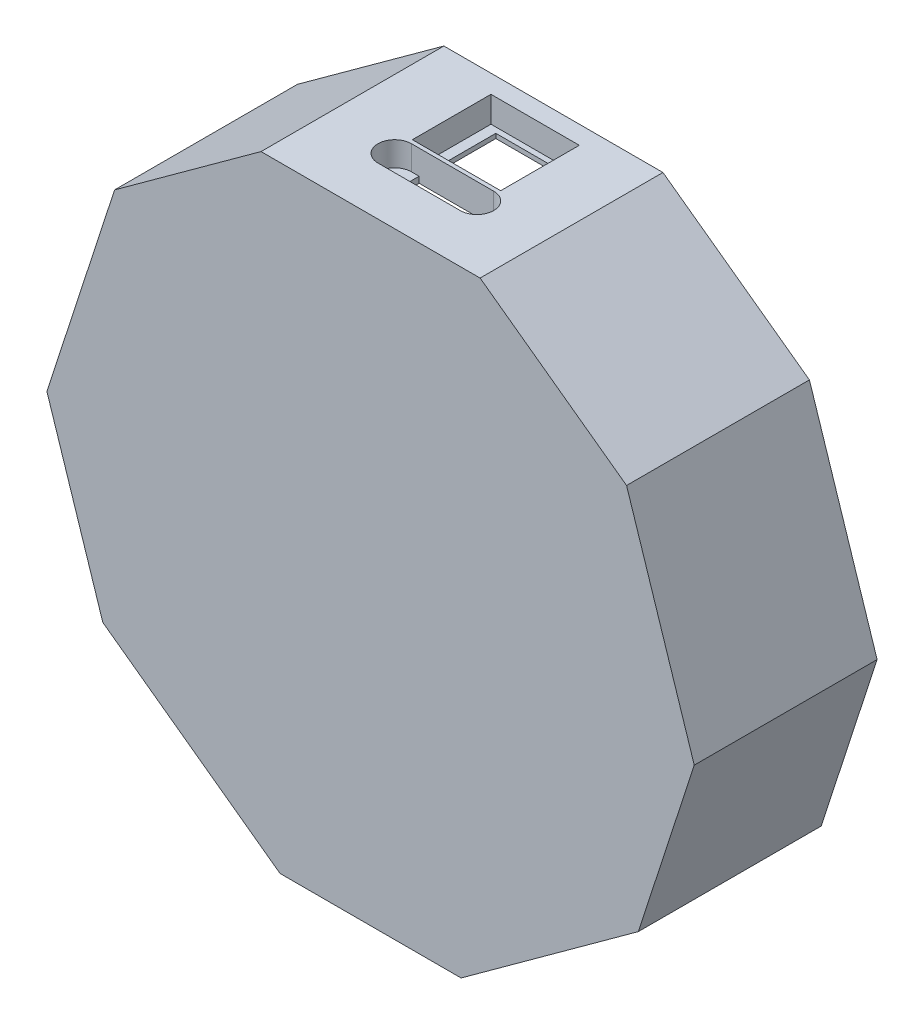
SolidWorks part; units mm, degrees
note: '?' marks a value the reader was unsure of.
ref_plane "Front Plane" through (0, 0, 0) normal (0, 0, 1) x (1, 0, 0)
ref_plane "Top Plane" through (0, 0, 0) normal (0, 1, 0) x (1, 0, 0)
ref_plane "Right Plane" through (0, 0, 0) normal (1, 0, 0) x (0, 0, -1)
sketch "Sketch2" plane through (0, 0, 0) normal (0, 1, 0) x (1, 0, 0)
  line L0 (15.061, 0) -> (15.061, 32)
  line L1 (-12.561, 2.5) -> (12.561, 2.5)
  line L2 (-12.561, 2.5) -> (-12.561, 32)
  line L4 (12.561, 2.5) -> (12.561, 32)
  line L5 (15.061, 32) -> (12.561, 32)
  line L7 (-15.061, 32) -> (-15.061, 0)
  line L8 (-15.061, 0) -> (15.061, 0)
  line L10 (-15.061, 32) -> (-12.561, 32)
  point P4 (0, 2.5)
  point P12 (0, 0)
  dimension "D1" = 2.5
  dimension "D2" = 2.5
  dimension "D3" = 29.5
  dimension "D4" = 25.122
extrude "Boss-Extrude1" add sketch "Sketch2" along normal blind 32.5
sketch "Sketch4" plane through (0, 0, 0) normal (0, -1, 0) x (1, 0, 0)
  line L10 (-7.561, -6) -> (-7.561, 0)
  line L13 (-12.561, -2.5) -> (-12.561, -32) construction
  line L18 (-12.561, -10) -> (-7.561, -6)
  line L23 (12.561, -32) -> (12.561, -2.5) construction
  line L26 (12.561, -10) -> (7.561, -6)
  line L33 (-15.061, -32) -> (-15.061, 0) construction
  line L36 (15.061, 0) -> (15.061, -32) construction
  line L38 (-7.561, 0) -> (-15.061, 0)
  line L39 (7.561, -6) -> (7.561, 0)
  line L40 (7.561, 0) -> (15.061, 0)
  line L41 (-15.061, 0) -> (-15.061, -32)
  line L42 (-15.061, -32) -> (-12.561, -32)
  line L43 (-12.561, -32) -> (-15.061, -32) construction
  line L44 (-12.561, -32) -> (-12.561, -10)
  line L45 (12.561, -10) -> (12.561, -32)
  line L46 (12.561, -32) -> (15.061, -32)
  line L47 (15.061, -32) -> (15.061, 0)
  circle A2 centre (-10.2499, -4.95) radius 1.05
  circle A5 centre (10.2499, -4.95) radius 1.05
  dimension "D4" = 6
  dimension "D5" = 2.1
  dimension "D1" = 7.5
  dimension "D2" = 7.5
  dimension "D3" = 10
extrude "Boss-Extrude2" add sketch "Sketch4" along normal blind 2.5
sketch "Sketch5" plane through (0, 32.5, 0) normal (0, 1, 0) x (1, 0, 0)
  line L0 (-15.061, 32) -> (-10.2499, 32)
  line L9 (-10.2499, 32) -> (-6.25, 26)
  line L13 (-15.061, 0) -> (15.061, 0) construction
  line L14 (15.061, 0) -> (-15.061, 0)
  line L15 (-15.061, 0) -> (-15.061, 32)
  line L20 (15.061, 0) -> (15.061, 32)
  line L21 (-6.25, 26) -> (6.25, 26)
  line L22 (6.25, 26) -> (10.2499, 32)
  line L23 (10.2499, 32) -> (15.061, 32)
  circle A0 centre (-10.2499, 4.95) radius 1.05 construction
  circle A1 centre (-10.2499, 8.7) radius 1.05
  circle A2 centre (10.2499, 8.7) radius 1.05
  point P6 (0, 26)
  dimension "D4" = 0
  dimension "D1" = 8.7
  dimension "D2" = 12.5
  dimension "D3" = 20.4998
  dimension "D5" = 6
extrude "Boss-Extrude3" add sketch "Sketch5" along normal blind 3
sketch "Sketch6" plane through (-15.061, 0, 0) normal (-1, 0, 0) x (0, 0, 1)
  line L0 (-12.5, 35.5) -> (-32, 2.5)
  line L1 (-32, 2.5) -> (-32, 35.5)
  line L2 (-32, 35.5) -> (-12.5, 35.5)
  line L3 (-32, 35.5) -> (-32, -2.5) construction
  line L4 (-32, 35.5) -> (0, 35.5) construction
  line L6 (0, -2.5) -> (-32, -2.5) construction
  line L7 (0, 35.5) -> (0, -2.5) construction
  dimension "D1" = 5
  dimension "D2" = 12.5
extrude "Cut-Extrude1" cut sketch "Sketch6" against normal through all
ref_plane "Plane1" through (0, 16.5, 0) normal (0, -1, 0) x (-1, 0, 0)
sketch "Sketch13" plane through (0, 0, 0) normal (0, 0, 1) x (1, 0, 0)
  line L1 (-15.061, 35.5) -> (15.061, 35.5)
  line L2 (-15.061, 35.5) -> (-15.061, -2.5)
  line L3 (-15.061, -2.5) -> (15.061, -2.5)
  line L4 (15.061, 35.5) -> (15.061, -2.5)
extrude "Boss-Extrude7" add sketch "Sketch13" along normal blind 2.5
sketch "Sketch8" plane through (0, 0, 2.5) normal (0, 0, 1) x (1, 0, 0)
  line L0 (0, -43.5) -> (-43.5926, 16.5)
  line L1 (-16.5671, 16.5) -> (16.5671, 16.5) construction
  line L2 (-43.5926, 16.5) -> (43.5926, 16.5)
  line L3 (43.5926, 16.5) -> (0, -43.5)
  dimension "D1" = 72
  dimension "D2" = 60
extrude "Boss-Extrude4" add sketch "Sketch8" along normal blind 5
sketch "Sketch9" plane through (0, 0, 2.5) normal (0, 0, 1) x (1, 0, 0)
  line L0 (43.5926, 16.5) -> (65.3888, 46.5)
  line L1 (65.3888, 46.5) -> (-65.3888, 46.5)
  line L2 (-65.3888, 46.5) -> (-43.5926, 16.5)
  line L3 (43.5926, 16.5) -> (-43.5926, 16.5)
  line L4 (0, -43.5) -> (43.5926, 16.5) construction
  line L5 (-43.5926, 16.5) -> (0, -43.5) construction
  dimension "D1" = 30
extrude "Boss-Extrude6" add sketch "Sketch9" along normal up to surface (5 mm away) up to face at (0, -3.5, 7.5)
sketch "Sketch10" plane through (0, 0, 2.5) normal (0, 0, -1) x (-1, 0, 0)
  line L1 (-65.3888, 46.5) -> (-54.093, 30.9526)
  line L2 (0, -43.5) -> (-65.3888, 46.5) construction
  line L13 (-54.093, 30.9526) -> (-32.6938, 46.5)
  line L15 (-65.3888, 46.5) -> (65.3888, 46.5) construction
  line L17 (-32.6938, 46.5) -> (-65.3888, 46.5)
  line L19 (54.093, 30.9526) -> (65.3888, 46.5)
  line L23 (65.3888, 46.5) -> (0, -43.5) construction
  line L34 (65.3888, 46.5) -> (32.6938, 46.5)
  line L35 (32.6938, 46.5) -> (54.093, 30.9526)
  dimension "D1" = 36
  dimension "D2" = 36
  dimension "D3" = 32.695
extrude "Cut-Extrude2" cut sketch "Sketch10" against normal through all
sketch "Sketch14" plane through (0, 0, -2.5) normal (0, 0, -1) x (-1, 0, 0)
  line L11 (-7.561, -2.5) -> (7.561, -2.5)
  line L12 (15.061, -2.5) -> (-15.061, -2.5) construction
  line L13 (7.561, -2.5) -> (7.561, 0)
  line L14 (12.561, 0) -> (7.561, 0) construction
  line L15 (7.561, -2.5) -> (7.561, 0) construction
  line L16 (7.561, 0) -> (12.561, 0)
  line L17 (12.561, 0) -> (12.561, 7.7837)
  line L18 (12.561, 2.5) -> (12.561, 32.5) construction
  line L19 (12.561, 7.7837) -> (-12.561, 7.7837)
  line L20 (-12.561, 32.5) -> (-12.561, 2.5) construction
  line L21 (-12.561, 7.7837) -> (-12.561, 0)
  line L22 (-12.561, 2.5) -> (-12.561, -2.5) construction
  line L23 (-7.561, 0) -> (-12.561, 0) construction
  line L24 (-12.561, 0) -> (-7.561, 0)
  line L25 (-7.561, 0) -> (-7.561, -2.5)
  line L26 (-7.561, -2.5) -> (-12.561, -2.5) construction
  line L27 (-15.061, 35.5) -> (15.061, 35.5) construction
  line L28 (-7.5, 35.5) -> (7.5, 35.5)
  line L29 (-7.5, 35.5) -> (-7.5, 40.5)
  line L30 (-7.5, 40.5) -> (7.5, 40.5)
  line L31 (7.5, 35.5) -> (7.5, 40.5)
  point P37 (0, 35.5)
  dimension "D1" = 15
  dimension "D2" = 5
extrude "Cut-Extrude3" cut sketch "Sketch14" against normal through all
sketch "Sketch15" plane through (0, -2.5, 0) normal (0, -1, 0) x (1, 0, 0)
  line L1 (15.061, -32) -> (-15.061, -32)
  line L2 (15.061, -32) -> (15.061, 2.5)
  line L3 (15.061, 2.5) -> (-15.061, 2.5)
  line L4 (-15.061, -32) -> (-15.061, 2.5)
  circle A0 centre (-10.2499, -4.95) radius 2.495
  circle A1 centre (10.341, -4.95) radius 2.495
  dimension "D1" = 4.99
  dimension "D2" = 4.99
extrude "Boss-Extrude8" add sketch "Sketch15" along normal blind 3
sketch "Sketch17" plane through (0, -5.5, 0) normal (0, -1, 0) x (1, 0, 0)
  line L0 (15.061, 2.5) -> (-15.061, 2.5) construction
  circle A0 centre (0, -37.5) radius 13.75
  dimension "D2" = 27.5
  dimension "D1" = 40
extrude "Cut-Extrude4" cut sketch "Sketch17" against normal through all
sketch "Sketch19" plane through (0, 0, -2.5) normal (0, 0, -1) x (-1, 0, 0)
  line L0 (-15.061, 35.5) -> (15.061, 35.5) construction
  line L1 (7.5, 35.5) -> (-7.5, 35.5)
  line L2 (7.5, 35.5) -> (7.5, 32.5)
  line L3 (7.5, 32.5) -> (-7.5, 32.5)
  line L4 (-7.5, 35.5) -> (-7.5, 32.5)
  line L5 (7.5, 35.5) -> (7.5, 40.5) construction
  line L6 (-7.5, 40.5) -> (-7.5, 35.5) construction
  line L7 (-12.561, 32.5) -> (12.561, 32.5) construction
  dimension "D1" = 0
  dimension "D2" = 0
  dimension "D3" = 0
extrude "Cut-Extrude6" cut sketch "Sketch19" along normal through all both and the other way through all
sketch "Sketch21" plane through (0, 35.5, 0) normal (0, 1, 0) x (1, 0, 0)
  circle A0 centre (-10.2499, 8.7) radius 2.25
  circle A1 centre (10.2499, 8.7) radius 2.25
  dimension "D1" = 4.5
  dimension "D2" = 4.5
extrude "Cut-Extrude8" cut sketch "Sketch21" against normal blind 1.5
ref_axis "Axis1" through (0, -43.5, 11.5724) along (0, 0, -1)?
sketch "Sketch20" plane through (0, 0, 2.5) normal (0, 0, -1) x (-1, 0, 0)
  circle A0 centre (0, -43.5) radius 10
  dimension "D1" = 20
extrude "Cut-Extrude7" cut sketch "Sketch20" against normal through all
pattern_circular "CirPattern2" count 5 over 360 about axis through (0, -43.5, 0) along (0, 0, 1) of bodies 147
combine bodies "Combine1" bodies to combine 154 155 156 147 153
chamfer "Chamfer1" distance 2 angle 30 71 edges at (52.9007, -116.3115, 7.5) (0, -135.5285, 7.5) (87.5243, -71.9384, 7.5) (24.0992, -76.6697, 7.5) (18.7169, -82.1252, 7.5) (17.4291, -84.6059, 7.5) (17.6942, -89.224, 7.5) (30.1438, -84.9894, 7.5) (38.0183, -74.4576, 7.5) (33.7082, -72.7785, 7.5) (30.9509, -73.2367, 7.5) (40.9552, -112.6297, 7.5) (49.374, -111.4574, 7.5) (53.0904, -103.813, 7.5) (44.6717, -104.9853, 7.5) (8.0902, -37.6221, 7.5) (-52.9007, -116.3115, 7.5) (-33.7082, -72.7785, 7.5) (-30.9509, -73.2367, 7.5) (-24.0992, -76.6697, 7.5) (-18.7169, -82.1252, 7.5) (-17.4291, -84.6059, 7.5) (-17.6942, -89.224, 7.5) (-30.1438, -84.9894, 7.5) (-38.0183, -74.4576, 7.5) (-44.6717, -104.9853, 7.5) (-40.9552, -112.6297, 7.5) (-49.374, -111.4574, 7.5) (-53.0904, -103.813, 7.5) (54.093, 30.9526, 7.5) (-54.093, 30.9526, 7.5) (-87.5243, -71.9384, 7.5) (-38.2619, -20.4892, 7.5) (-37.8457, -23.2531, 7.5) (-38.9933, -30.8303, 7.5) (-42.5186, -37.635, 7.5) (-44.48, -39.6263, 7.5) (-48.9539, -40.8013, 7.5) (-48.7737, -27.6525, 7.5) (-41.1908, -16.9089, 7.5) (-72.2803, -20.0147, 7.5) (-78.4021, -25.9116, 7.5) (-79.8887, -17.5426, 7.5) (-73.7669, -11.6457, 7.5) (10.061, 0, 7.5) (7.561, -1.25, 7.5) (0, -2.5, 7.5) (-7.561, -1.25, 7.5) (-10.061, 0, 7.5) (-12.561, 3.8918, 7.5) (0, 7.7837, 7.5) (12.561, 3.8918, 7.5) (0, 32.5, 7.5) (-7.5, 36.5, 7.5) (0, 40.5, 7.5) (7.5, 36.5, 7.5) (44.48, -39.6263, 7.5) (42.5186, -37.635, 7.5) (38.9933, -30.8303, 7.5) (37.8457, -23.2531, 7.5) (38.2619, -20.4892, 7.5) (41.1908, -16.9089, 7.5) (48.7737, -27.6525, 7.5) (48.9539, -40.8013, 7.5) (72.2803, -20.0147, 7.5) (73.7669, -11.6457, 7.5) (79.8887, -17.5426, 7.5) (78.4021, -25.9116, 7.5) (-85.5951, -15.6885, 7.5) (0, 46.5, 7.5) (85.5951, -15.6885, 7.5)
sketch "Sketch22" plane through (0, 0, 2.5) normal (0, 0, -1) x (-1, 0, 0)
  circle A0 centre (0, -123.5) radius 1.575
  dimension "D1" = 80
  dimension "D2" = 3.15
extrude "Cut-Extrude9" cut sketch "Sketch22" against normal through all
sketch "Sketch23" plane through (0, 0, 2.5) normal (0, 0, -1) x (-1, 0, 0)
  circle A0 centre (0, -123.5) radius 2.6
  dimension "D1" = 5.2
extrude "Cut-Extrude10" cut sketch "Sketch23" against normal blind 3
pattern_circular "CirPattern3" count 5 over 360 about axis through (0, -43.5, 0) along (0, 0, 1) of "Cut-Extrude9", "Cut-Extrude10"
sketch "Sketch24" plane through (0, 0, 2.5) normal (0, 0, -1) x (-1, 0, 0)
  line L0 (-32.6938, 46.5) -> (32.6938, 46.5)
  line L1 (32.6938, 46.5) -> (75.4921, 15.4052)
  line L2 (75.4921, 15.4052) -> (95.698, -46.7821)
  line L3 (95.698, -46.7821) -> (79.3505, -97.0946)
  line L4 (79.3505, -97.0946) -> (26.4508, -135.5285)
  line L5 (26.4508, -135.5285) -> (-26.4508, -135.5285)
  line L6 (-26.4508, -135.5285) -> (-79.3505, -97.0946)
  line L7 (-79.3505, -97.0946) -> (-95.698, -46.7821)
  line L8 (-95.698, -46.7821) -> (-75.4921, 15.4052)
  line L9 (-75.4921, 15.4052) -> (-32.6938, 46.5)
  line L10 (87.857, -103.2749) -> (106.2127, -46.7821)
  line L11 (106.2127, -46.7821) -> (83.9986, 21.5855)
  line L12 (83.9986, 21.5855) -> (35.943, 56.5)
  line L13 (35.943, 56.5) -> (-35.943, 56.5)
  line L14 (-35.943, 56.5) -> (-83.9986, 21.5855)
  line L15 (-83.9986, 21.5855) -> (-106.2127, -46.7821)
  line L16 (-106.2127, -46.7821) -> (-87.857, -103.2749)
  line L17 (-87.857, -103.2749) -> (-29.7, -145.5285)
  line L18 (-29.7, -145.5285) -> (29.7, -145.5285)
  line L19 (29.7, -145.5285) -> (87.857, -103.2749)
  dimension "D1" = 10
  dimension "D2" = 10
  dimension "D3" = 10
  dimension "D4" = 10
  dimension "D5" = 10
  dimension "D6" = 10
  dimension "D7" = 10
  dimension "D8" = 10
  dimension "D9" = 10
  dimension "D10" = 10
extrude "Boss-Extrude9" add sketch "Sketch24" against normal blind 55
sketch "Sketch25" plane through (0, 0, 7.5) normal (0, 0, 1) x (1, 0, 0)
  line L0 (-32.6938, 46.5) -> (32.6938, 46.5)
  line L1 (32.6938, 46.5) -> (75.4921, 15.4052)
  line L2 (75.4921, 15.4052) -> (95.698, -46.7821)
  line L3 (95.698, -46.7821) -> (79.3505, -97.0946)
  line L4 (79.3505, -97.0946) -> (26.4508, -135.5285)
  line L5 (26.4508, -135.5285) -> (-26.4508, -135.5285)
  line L6 (-26.4508, -135.5285) -> (-79.3505, -97.0946)
  line L7 (-79.3505, -97.0946) -> (-95.698, -46.7821)
  line L8 (-95.698, -46.7821) -> (-75.4921, 15.4052)
  line L9 (-75.4921, 15.4052) -> (-32.6938, 46.5)
extrude "Cut-Extrude11" cut sketch "Sketch25" against normal through all both and the other way through all
sketch "Sketch26" plane through (0, 0, 57.5) normal (0, 0, 1) x (1, 0, 0)
  line L10 (-83.9986, 21.5855) -> (-35.943, 56.5)
  line L11 (-35.943, 56.5) -> (35.943, 56.5)
  line L12 (35.943, 56.5) -> (83.9986, 21.5855)
  line L13 (83.9986, 21.5855) -> (106.2127, -46.7821)
  line L14 (106.2127, -46.7821) -> (87.857, -103.2749)
  line L15 (87.857, -103.2749) -> (29.7, -145.5285)
  line L16 (29.7, -145.5285) -> (-29.7, -145.5285)
  line L17 (-29.7, -145.5285) -> (-87.857, -103.2749)
  line L18 (-87.857, -103.2749) -> (-106.2127, -46.7821)
  line L19 (-106.2127, -46.7821) -> (-83.9986, 21.5855)
extrude "Boss-Extrude10" add sketch "Sketch26" along normal blind 5
sketch "Sketch29" plane through (0, 0, 57.5) normal (0, 0, -1) x (-1, 0, 0)
  line L0 (-41.2003, 46.5) -> (41.2003, 46.5)
  line L1 (41.2003, 46.5) -> (79.7454, 18.4954)
  line L2 (79.7454, 18.4954) -> (100.9553, -46.7821)
  line L3 (100.9553, -46.7821) -> (83.6038, -100.1847)
  line L4 (83.6038, -100.1847) -> (28.0754, -140.5285)
  line L5 (28.0754, -140.5285) -> (-28.0754, -140.5285)
  line L6 (-28.0754, -140.5285) -> (-83.6038, -100.1847)
  line L7 (-83.6038, -100.1847) -> (-100.9553, -46.7821)
  line L8 (-100.9553, -46.7821) -> (-79.7454, 18.4954)
  line L9 (-79.7454, 18.4954) -> (-41.2003, 46.5)
  line L11 (32.6938, 46.5) -> (-32.6938, 46.5) construction
  line L12 (75.4921, 15.4052) -> (32.6938, 46.5) construction
  line L13 (95.698, -46.7821) -> (75.4921, 15.4052) construction
  line L14 (79.3505, -97.0946) -> (95.698, -46.7821) construction
  line L15 (26.4508, -135.5285) -> (79.3505, -97.0946) construction
  line L16 (-26.4508, -135.5285) -> (26.4508, -135.5285) construction
  line L17 (-79.3505, -97.0946) -> (-26.4508, -135.5285) construction
  line L18 (-95.698, -46.7821) -> (-79.3505, -97.0946) construction
  line L19 (-75.4921, 15.4052) -> (-95.698, -46.7821) construction
  line L21 (-32.6938, 46.5) -> (-75.4921, 15.4052) construction
  line L22 (75.4921, 15.4052) -> (32.6938, 46.5) construction
  line L23 (79.3505, -97.0946) -> (95.698, -46.7821) construction
  line L24 (-95.698, -46.7821) -> (-79.3505, -97.0946) construction
  line L25 (-32.6938, 46.5) -> (-75.4921, 15.4052) construction
  dimension "D1" = 0
  dimension "D2" = 5
  dimension "D3" = 5
  dimension "D4" = 5
  dimension "D5" = 5
  dimension "D6" = 5
  dimension "D7" = 5
  dimension "D8" = 5
  dimension "D9" = 5
  dimension "D10" = 5
extrude "Cut-Extrude12" cut sketch "Sketch29" along normal offset from surface (50 mm away) 5
chamfer "Chamfer2" distance 3 angle 45 9 edges at (60.4729, 32.4977, 7.5) (90.3504, -14.1434, 7.5) (92.2796, -73.4834, 7.5) (55.8396, -120.3566, 7.5) (0, -140.5285, 7.5) (-55.8396, -120.3566, 7.5) (-92.2796, -73.4834, 7.5) (-90.3504, -14.1434, 7.5) (-60.4729, 32.4977, 7.5)
sketch "Sketch30" plane through (0, 56.5, 0) normal (0, 1, 0) x (1, 0, 0)
  line L1 (-14.49, -8.5) -> (14.49, -8.5)
  line L2 (-14.49, -8.5) -> (-14.49, -34.3)
  line L3 (-14.49, -34.3) -> (14.49, -34.3)
  line L4 (14.49, -8.5) -> (14.49, -34.3)
  line L5 (-35.943, -2.5) -> (35.943, -2.5) construction
  point P7 (0, -8.5)
  dimension "D1" = 28.98
  dimension "D2" = 25.8
  dimension "D3" = 6
extrude "Cut-Extrude15" cut sketch "Sketch30" against normal offset from surface (8.5 mm away) 1.5
sketch "Sketch33" plane through (0, 48, 0) normal (0, 1, 0) x (1, 0, 0)
  line L0 (14.49, -8.5) -> (-14.49, -8.5) construction
  line L1 (-11.1125, -10.2875) -> (11.1125, -10.2875)
  line L2 (-11.1125, -10.2875) -> (-11.1125, -32.5125)
  line L3 (-11.1125, -32.5125) -> (11.1125, -32.5125)
  line L4 (11.1125, -10.2875) -> (11.1125, -32.5125)
  line L5 (14.49, -34.3) -> (14.49, -8.5) construction
  point P6 (0, -8.5)
  point P7 (0, -10.2875)
  point P10 (14.49, -21.4)
  point P11 (11.1125, -21.4)
  dimension "D1" = 22.225
  dimension "D2" = 22.225
extrude "Cut-Extrude16" cut sketch "Sketch33" against normal up to next
sketch "Sketch32" plane through (0, 56.5, 0) normal (0, 1, 0) x (1, 0, 0)
  line L0 (-13.5, -41.0826) -> (13.5, -41.0826) construction
  line L4 (-13.5, -35.5826) -> (13.5, -35.5826)
  line L5 (-13.5, -46.5826) -> (13.5, -46.5826)
  arc A2 (-13.5, -35.5826) -> (-13.5, -46.5826) centre (-13.5, -41.0826) ccw
  arc A3 (13.5, -46.5826) -> (13.5, -35.5826) centre (13.5, -41.0826) ccw
  point P2 (0, -41.0826)
  point P7 (-19, -41.0826)
  point P8 (19, -41.0826)
  point P10 (0, -35.5826)
  dimension "D1" = 38
  dimension "D2" = 11
extrude "Cut-Extrude14" cut sketch "Sketch32" against normal offset from surface (8 mm away) 8
sketch "Sketch34" plane through (0, 48.5, 0) normal (0, 1, 0) x (1, 0, 0)
  line L0 (13.5, -35.5826) -> (-13.5, -35.5826) construction
  line L1 (-11, -35.5826) -> (11, -35.5826)
  line L2 (-11, -35.5826) -> (-11, -46.5826)
  line L3 (-11, -46.5826) -> (11, -46.5826)
  line L4 (11, -35.5826) -> (11, -46.5826)
  line L5 (-13.5, -46.5826) -> (13.5, -46.5826) construction
  line L8 (13.5, -46.5826) -> (-13.5, -46.5826) construction
  circle A0 centre (-13.6, -41.3505) radius 2.25
  circle A1 centre (13.6, -41.3505) radius 2.25
  point P10 (0, -46.5826)
  point P11 (0, -46.5826)
  dimension "D2" = 27.2
  dimension "D4" = 4.5
  dimension "D5" = 4.5
  dimension "D1" = 22
  dimension "D3" = 13.6
extrude "Cut-Extrude17" cut sketch "Sketch34" against normal up to next
equation "\"worth\"=6.3146"
equation "\"butt\"=10"
equation "\"butt5\"=5"
equation "\"D1@Sketch29\"=0"
equation "\"D2@Sketch29\"=\"butt5\""
equation "\"D3@Sketch29\"=\"butt5\""
equation "\"D4@Sketch29\"=\"butt5\""
equation "\"D5@Sketch29\"=\"butt5\""
equation "\"D6@Sketch29\"=\"butt5\""
equation "\"D7@Sketch29\"=\"butt5\""
equation "\"D8@Sketch29\"=\"butt5\""
equation "\"D9@Sketch29\"=\"butt5\""
equation "\"D10@Sketch29\"=\"butt5\""
